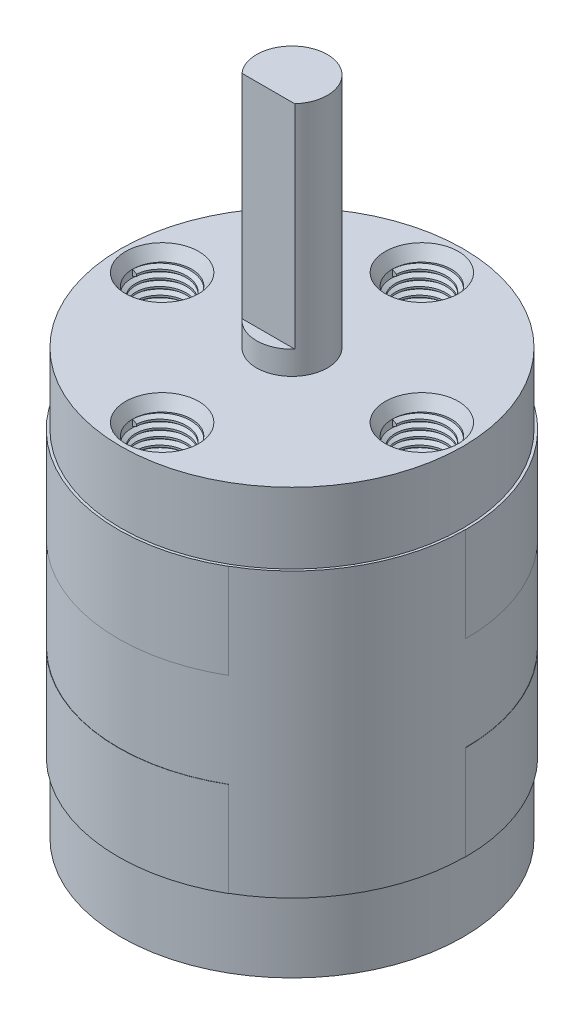
SolidWorks part; units mm, degrees
ref_plane "前视基准面" through (0, 0, 0) normal (0, 0, 1) x (1, 0, 0)
ref_plane "上视基准面" through (0, 0, 0) normal (0, 1, 0) x (1, 0, 0)
ref_plane "右视基准面" through (0, 0, 0) normal (1, 0, 0) x (0, 0, -1)
sketch "草图1" plane through (0, 0, 0) normal (0, 1, 0) x (1, 0, 0)
  circle A0 centre (0, 0) radius 7.25
extrude "凸台-拉伸1" add sketch "草图1" along normal blind 18
sketch "草图2" plane through (0, 18, 0) normal (0, 1, 0) x (1, 0, 0)
  circle A0 centre (0, 0) radius 1.5
extrude "凸台-拉伸2" add sketch "草图2" along normal blind 10
sketch "草图3" plane through (0, 28, 0) normal (0, 1, 0) x (1, 0, 0)
  line L1 (1.118, -1) -> (-1.118, -1)
  circle A0 centre (0, 0) radius 1.5 construction
  arc A1 (-1.118, -1) -> (1.118, -1) centre (0, 0) ccw
extrude "切除-拉伸1" cut sketch "草图3" against normal blind 9
sketch "草图4" plane through (0, 18, 0) normal (0, 1, 0) x (1, 0, 0)
  circle A0 centre (5.5, 0) radius 1.25
  circle A1 centre (0, -5.5) radius 1.25
  circle A2 centre (-5.5, 0) radius 1.25
  circle A3 centre (0, 5.5) radius 1.25
  point P11 (0, 0)
  dimension "D1" = 4
extrude "切除-拉伸2" cut sketch "草图4" against normal blind 5
sketch "草图8" plane through (0, 0, 0) normal (0, 0, 1) x (1, 0, 0)
  line L0 (6.75, 18) -> (7.05, 18)
  line L1 (7.25, 18) -> (-7.25, 18) construction
  line L3 (6.75, 17.5) -> (7.05, 18)
  line L4 (6.75, 18) -> (5.5, 18)
  line L5 (6.75, 18) -> (4.25, 18) construction
  line L6 (5.5, 18) -> (5.5, 17.5)
  line L7 (5.5, 17.5) -> (6.75, 17.5)
revolve "切除-旋转1" cut sketch "草图8" angle 360 about L6
sketch3d "3D草图5"
  line L0 (0, 0, 0) -> (0, 11.8755, 0) construction
pattern_circular "阵列(圆周)1" count 4 over 360 about axis through (0, 0, 0) along (0, 1, 0) of "切除-旋转1"
sketch "草图9" plane through (0, 0, 0) normal (0, 0, 1) x (1, 0, 0)
  line L1 (7.25, 0) -> (7.25, 18) construction
  line L2 (7.25, 15) -> (7.35, 15)
  line L3 (7.35, 15) -> (7.35, 3)
  line L4 (7.35, 3) -> (7.25, 3)
  line L5 (7.25, 15) -> (7.25, 3)
revolve "旋转1" add sketch "草图9" angle 360 about L0
sketch "草图11" plane through (0, 0, 0) normal (0, 0, 1) x (1, 0, 0)
  line L6 (7.35, 15) -> (7.36, 15)
  line L7 (7.35, 15) -> (7.35, 11)
  line L8 (7.35, 11) -> (7.36, 11)
  line L9 (7.36, 15) -> (7.36, 11)
  line L10 (7.35, 3) -> (7.36, 3)
  line L11 (7.35, 3) -> (7.35, 7)
  line L12 (7.35, 7) -> (7.36, 7)
  line L13 (7.36, 3) -> (7.36, 7)
revolve "旋转2" add sketch "草图11" angle 300 about L0
thread "螺纹线1" pitch 0.3175 start angle 0, offset 0, length 5, pitch 0.3175, diameter 2.5
ref_plane "基准面1" through (-6.75, 17.5, 0) normal (0, 0, 1) x (-1, 0, 0)
sketch "螺纹线轮廓1" plane through (-6.75, 17.5, 0) normal (0, 0, 1) x (-1, 0, 0)
  line L0 (0, 0) -> (0, 0.3175) construction
  line L11 (0, 0) -> (0, 0.2778)
  line L12 (0, 0.2778) -> (-0.1719, 0.1786)
  line L13 (-0.1719, 0.1786) -> (-0.1719, 0.0992)
  line L15 (-0.1719, 0.0992) -> (0, 0)
  line L17 (-0.1719, 0.1389) -> (0, 0.1389) construction
  point P2 (0, 0)
  dimension "Pitch" = 0.3175
  dimension "Profile_Angle" = 60
  dimension "Profile_Land" = 0.0794
  dimension "Profile_Height" = 0.1719
thread "螺纹线2" pitch 0.3175 profile "螺纹线轮廓2" start angle 0, offset 0, length 5, pitch 0.3175, diameter 2.5
ref_plane "基准面2" through (-1.25, 17.5, -5.5) normal (0, 0, 1) x (-1, 0, 0)
sketch "螺纹线轮廓2" plane through (-1.25, 17.5, -5.5) normal (0, 0, 1) x (-1, 0, 0)
  line L0 (0, 0) -> (0, 0.3175) construction
  line L11 (0, 0) -> (0, 0.2778)
  line L12 (0, 0.2778) -> (-0.1719, 0.1786)
  line L13 (-0.1719, 0.1786) -> (-0.1719, 0.0992)
  line L15 (-0.1719, 0.0992) -> (0, 0)
  line L17 (-0.1719, 0.1389) -> (0, 0.1389) construction
  point P2 (0, 0)
  dimension "Pitch" = 0.3175
  dimension "Profile_Angle" = 60
  dimension "Profile_Land" = 0.0794
  dimension "Profile_Height" = 0.1719
thread "螺纹线3" pitch 0.3175 profile "螺纹线轮廓3" start angle 0, offset 0, length 5, pitch 0.3175, diameter 2.5
ref_plane "基准面3" through (4.25, 17.5, 0) normal (0, 0, 1) x (-1, 0, 0)
sketch "螺纹线轮廓3" plane through (4.25, 17.5, 0) normal (0, 0, 1) x (-1, 0, 0)
  line L0 (0, 0) -> (0, 0.3175) construction
  line L11 (0, 0) -> (0, 0.2778)
  line L12 (0, 0.2778) -> (-0.1719, 0.1786)
  line L13 (-0.1719, 0.1786) -> (-0.1719, 0.0992)
  line L15 (-0.1719, 0.0992) -> (0, 0)
  line L17 (-0.1719, 0.1389) -> (0, 0.1389) construction
  point P2 (0, 0)
  dimension "Pitch" = 0.3175
  dimension "Profile_Angle" = 60
  dimension "Profile_Land" = 0.0794
  dimension "Profile_Height" = 0.1719
thread "螺纹线4" pitch 0.3175 profile "螺纹线轮廓4" start angle 0, offset 0, length 5, pitch 0.3175, diameter 2.5
ref_plane "基准面4" through (-1.25, 17.5, 5.5) normal (0, 0, 1) x (-1, 0, 0)
sketch "螺纹线轮廓4" plane through (-1.25, 17.5, 5.5) normal (0, 0, 1) x (-1, 0, 0)
  line L0 (0, 0) -> (0, 0.3175) construction
  line L11 (0, 0) -> (0, 0.2778)
  line L12 (0, 0.2778) -> (-0.1719, 0.1786)
  line L13 (-0.1719, 0.1786) -> (-0.1719, 0.0992)
  line L15 (-0.1719, 0.0992) -> (0, 0)
  line L17 (-0.1719, 0.1389) -> (0, 0.1389) construction
  point P2 (0, 0)
  dimension "Pitch" = 0.3175
  dimension "Profile_Angle" = 60
  dimension "Profile_Land" = 0.0794
  dimension "Profile_Height" = 0.1719
